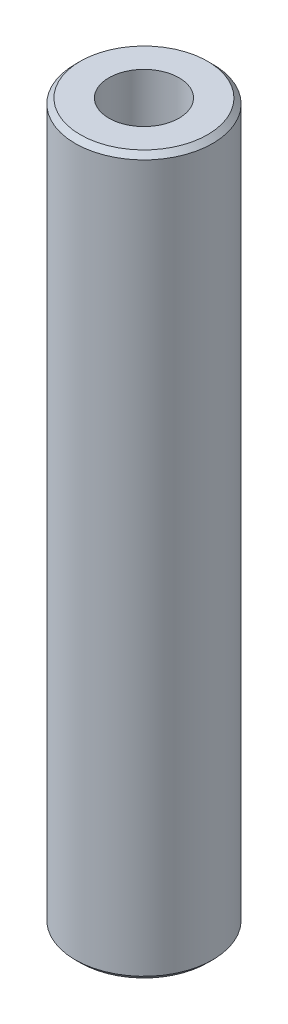
SolidWorks part; units mm, degrees
ref_plane "Front Plane" through (0, 0, 0) normal (0, 0, 1) x (1, 0, 0)
ref_plane "Top Plane" through (0, 0, 0) normal (0, 1, 0) x (1, 0, 0)
ref_plane "Right Plane" through (0, 0, 0) normal (1, 0, 0) x (0, 0, -1)
sketch "Sketch1" plane through (0, 0, 0) normal (0, 1, 0) x (1, 0, 0)
  circle A0 centre (0, 0) radius 57.5
  dimension "SHAFT_OD" = 115
extrude "Boss-Extrude1" add sketch "Sketch1" along normal blind 600
sketch "Sketch2" plane through (0, 0, 0) normal (0, 1, 0) x (1, 0, 0)
  circle A0 centre (0, 0) radius 29.3424
  dimension "BORE_D" = 58.6849
extrude "Cut-Extrude1" cut sketch "Sketch2" along normal through all
chamfer "Chamfer1" distance 4.2386 angle 45 2 edges at (0, 600, 57.5) (0, 0, 57.5)
